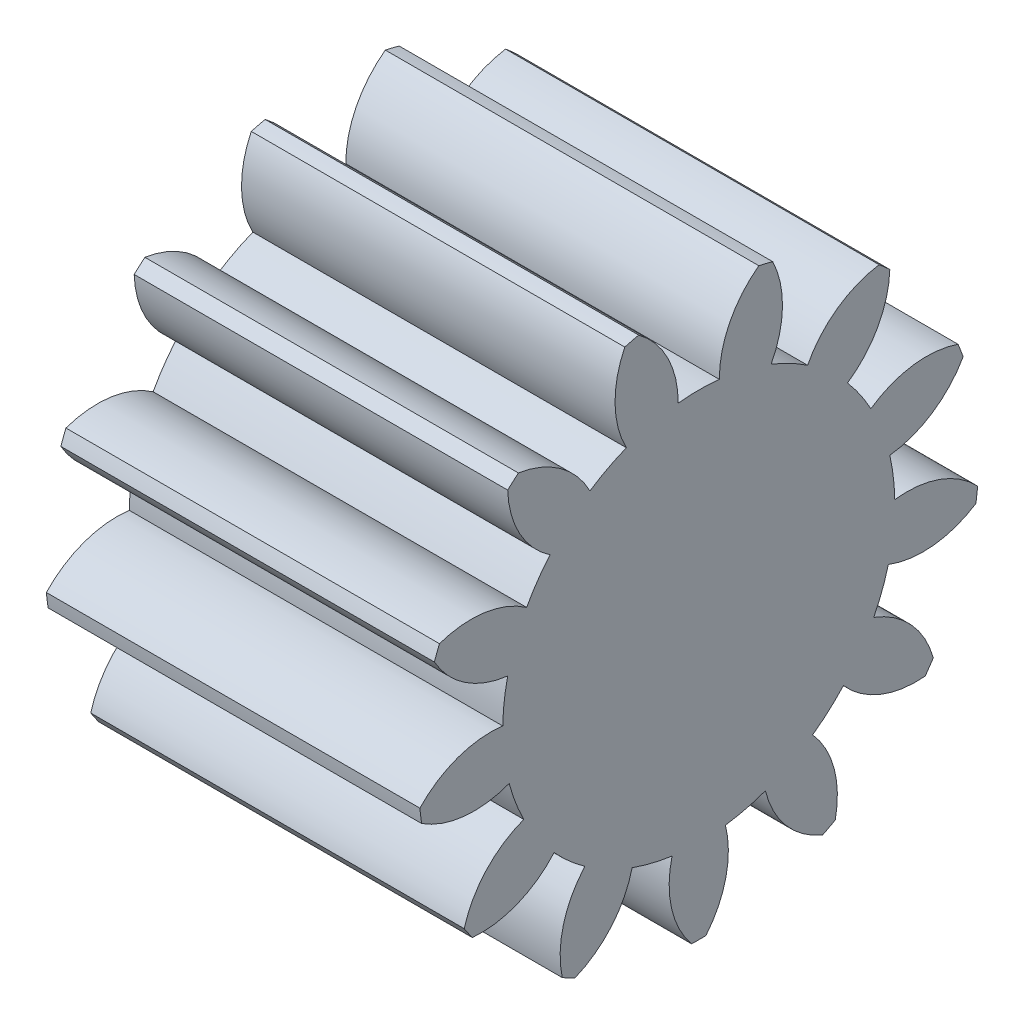
SolidWorks part; units mm, degrees
ref_plane "Plane1" through (0, 0, 0) normal (0, 0, 1) x (1, 0, 0)
ref_plane "Plane2" through (0, 0, 0) normal (0, 1, 0) x (1, 0, 0)
ref_plane "Plane3" through (0, 0, 0) normal (1, 0, 0) x (0, 0, -1)
sketch "HoldingSke" plane through (0, 0, 0) normal (0, 1, 0) x (1, 0, 0)
  line L0 (0, 0) -> (1.624, -0.3749)
  line L1 (-15, 0) -> (100, 0) construction
  line L2 (0, 0) -> (-2.1039, 2.3779)
  line L3 (0, 0) -> (-11.863, 4.5341)
  line L4 (0, 0) -> (8.4147, 1.9427)
  line L5 (0, 0) -> (-46.8476, -17.4728)
  line L6 (0, 0) -> (-1.8237, -1.2305)
  line L7 (-2.1039, 2.3779) -> (8.6586, 51.2059)
  line L8 (-76.2, 54.61) -> (-75.7, 54.61)
  line L9 (-71.009, 38.7566) -> (-53.1078, 45.2721)
  line L10 (-76.2, 71.12) -> (104.1128, 71.12)
  line L11 (0, 0) -> (-2.2, 0)
  line L12 (-76.2, 101.6) -> (-76.177, 101.6)
  line L13 (24.9733, 27.94) -> (52.9518, 28.4284)
  line L14 (24.9733, 27.94) -> (24.9743, 27.94)
  line L15 (24.9733, 27.94) -> (100.4006, 29.5858)
  line L16 (-63.627, -0.6) -> (-12.827, -0.6)
  circle A0 centre (0, 0) radius 1.5
  circle A1 centre (0, 0) radius 3.149
  circle A2 centre (0, 0) radius 37.5
  circle A3 centre (0, 0) radius 1.5
  dimension "MHD" = 6.298
  dimension "Hub_dia" = 75
  dimension "Bore" = 3
  dimension "MBD" = 3
  dimension "Num_teeth" = 13
  dimension "Pitch" = 1.6667
  dimension "Overall_len" = 50
  dimension "Show_teeth" = 13
  dimension "Thickness" = 2.2
  dimension "OAL" = 50.0001
  dimension "T_dim" = 0.5
  dimension "Ap" = 20
  dimension "H" = 19.05
  dimension "Pitch_radius" = 180.3128
  dimension "Width" = 2.2
  dimension "Backlash" = 0.023
  dimension "Addendum_fac" = 1
  dimension "Dedendum_fac" = 1.25
  dimension "Clearance_fac" = 0.25
  dimension "Dedendum_add" = 0.001
  dimension "Module" = 0.6
sketch "BasProSke" plane through (0, 0, 0) normal (0, 1, 0) x (1, 0, 0)
  line L0 (-10, 0) -> (60, 0) construction
  line L1 (0, 0) -> (0, 4.5)
  line L2 (0, 0) -> (6, 0)
  line L3 (6, 0) -> (6, 4.5)
  line L4 (6, 4.5) -> (0, 4.5)
  dimension "Thickness" = 6
  dimension "Diameter" = 9
revolve "Base-Revolve" add sketch "BasProSke" angle 360 about L0
sketch "TooCutSke" plane through (0, 0, 0) normal (1, 0, 0) x (0, 0, -1)
  line L1 (0, 0) -> (0, 107) construction
  line L2 (0, 0) -> (-0.5103, 3.8665) construction
  line L3 (0, 0) -> (-1.8553, 7.5272) construction
  line L4 (-0.5103, 3.8665) -> (-0.9276, 3.7636) construction
  arc A0 (0.3306, 3.1316) -> (-0.3306, 3.1316) centre (0, 0) ccw
  arc A1 (0.9926, 4.4152) -> (-0.9926, 4.4152) centre (0, 0) ccw
  circle A2 centre (0, 0) radius 3.9 construction
  circle A3 centre (0, 0) radius 3.6648 construction
  arc A4 (-0.3306, 3.1316) -> (-0.9926, 4.4152) centre (-1.8906, 3.1395) ccw
  arc A5 (0.9926, 4.4152) -> (0.3306, 3.1316) centre (1.8906, 3.1395) ccw
  dimension "Root_dia" = 6.298
  dimension "Overcut_dia" = 9.0508
  dimension "Pitch_dia" = 7.8
  dimension "Base_dia" = 7.3296
  dimension "Flank_rad" = 1.56
  dimension "Half_ang" = 13.846
  dimension "Half_CT" = 0.4298
extrude "ToothCut" cut sketch "TooCutSke" along normal through all
fillet "Breaks" [suppressed] radius 0.012 tangent propagation no
fillet "RootFillets" [suppressed] radius 0.151
pattern_circular "TeethCuts" count 13 over 360 about axis through (-10, 0, 0) along (1, 0, 0) of "ToothCut", "RootFillets", "Breaks"
sketch "HubNeaOneSke" plane through (0, 0, 0) normal (-1, 0, 0) x (0, 0, 1)
  circle A0 centre (0, 0) radius 3.149
  dimension "Diameter" = 6.298
extrude "HubNearOne" [suppressed] add sketch "HubNeaOneSke" along normal blind 44.0001
sketch "HubNeaBotSke" plane through (0, 0, 0) normal (-1, 0, 0) x (0, 0, 1)
  circle A0 centre (0, 0) radius 3.149
  dimension "Diameter" = 6.298
extrude "HubNearBoth" [suppressed] add sketch "HubNeaBotSke" along normal blind 22
ref_plane "FarPln" through (6, 0, 0) normal (1, 0, 0) x (0, 0, -1)
sketch "HubFarSke" plane through (6, 0, 0) normal (1, 0, 0) x (0, 0, -1)
  circle A0 centre (0, 0) radius 3.149
  dimension "Diameter" = 6.298
extrude "HubFar" [suppressed] add sketch "HubFarSke" along normal blind 22
sketch "BorSke" plane through (0, 0, 0) normal (1, 0, 0) x (0, 0, -1)
  line L0 (1.118, 1) -> (-1.118, 1) construction
  line L1 (1.118, -1) -> (-1.118, -1) construction
  line L2 (1.118, 1) -> (-1.118, 1)
  line L3 (1.118, -1) -> (-1.118, -1)
  circle A0 centre (0, 0) radius 1.5 construction
  arc A1 (-1.118, -1) -> (-1.118, 1) centre (0, 0) ccw
  arc A2 (1.118, 1) -> (1.118, -1) centre (0, 0) ccw
  dimension "Diameter" = 3
extrude "Bore" cut sketch "BorSke" along normal mid plane 100.0001 rebuild error yes
sketch "KeySke" plane through (0, 0, 0) normal (1, 0, 0) x (0, 0, -1)
  line L0 (-0.6, 0) -> (-0.6, 2)
  line L1 (-0.6, 2) -> (0.6, 2)
  line L2 (0.6, 2) -> (0.6, 0)
  line L3 (0, 0) -> (0, 34) construction
  line L4 (-0.6, 0) -> (0.6, 0)
  dimension "Offset" = 2
  dimension "Width" = 1.2
extrude "Keyway" [suppressed] cut sketch "KeySke" along normal mid plane 100.0001
pattern_circular "Keyway2" [suppressed] count 2 every 90 about axis through (-10, 0, 0) along (1, 0, 0) reverse direction yes
equation "' \"Module@HoldingSke\" = 6.35"
equation "' \"Num_teeth@HoldingSke\" = 12"
equation "' \"Ap@HoldingSke\" =  20"
equation "' \"Ap@HoldingSke\" = 20"
equation "' \"Width@HoldingSke\" = 0.5 * 25.4"
equation "' \"Hub_dia@HoldingSke\"= 1 * 25.4"
equation "' \"Hub_dia@HoldingSke\" = 1 * 25.4"
equation "' \"Overall_len@HoldingSke\" = 1.0 * 25.4"
equation "' \"Bore@HoldingSke\" = 0.75 * 25.4"
equation "' \"T_dim@HoldingSke\" = 0.1 * 25.4"
equation "' \"Width@KeySke\" = 0.25 * 25.4"
equation "' \"Show_teeth@HoldingSke\" = 13"
equation "' \"Backlash@HoldingSke\" = 0.009 * 25.4"
equation "' \"Addendum_fac@HoldingSke\" = 1.0"
equation "' \"Dedendum_fac@HoldingSke\" = 1.25"
equation "' \"Dedendum_add@HoldingSke\" = 0.00005 * 25.4"
equation "' \"Clearance_fac@HoldingSke\" = 0.25"
equation "\"Pitch@HoldingSke\" = 1 / \"Module@HoldingSke\""
equation "\"Overcut_dia@TooCutSke\" = (\"Num_teeth@HoldingSke\" + 2 * \"Addendum_fac@HoldingSke\") / \"Pitch@HoldingSke\" + 0.002 * 25.4"
equation "\"Pitch_dia@TooCutSke\" = \"Num_teeth@HoldingSke\" / \"Pitch@HoldingSke\""
equation "\"Base_dia@TooCutSke\" = \"Num_teeth@HoldingSke\" / \"Pitch@HoldingSke\" * cos((\"Ap@HoldingSke\"  * 3.14159265 / 180))"
equation "\"Root_dia@TooCutSke\" = (\"Num_teeth@HoldingSke\" + 2) / \"Pitch@HoldingSke\" - 2 * (\"Addendum_fac@HoldingSke\" + \"Dedendum_fac@HoldingSke\") / \"Pitch@HoldingSke\" - \"Dedendum_add@HoldingSke\" * 2"
equation "\"Half_ang@TooCutSke\" = 180 / \"Num_teeth@HoldingSke\""
equation "\"Half_CT@TooCutSke\" = \"Num_teeth@HoldingSke\" / \"Pitch@HoldingSke\" * sin((3.14159265 / 2 / \"Num_teeth@HoldingSke\")) / 2 - 7 * \"Backlash@HoldingSke\" / 4"
equation "\"Flank_rad@TooCutSke\" = \"Num_teeth@HoldingSke\" / \"Pitch@HoldingSke\" / 5"
equation "\"Radius@RootFillets\" = \"Clearance_fac@HoldingSke\" / \"Pitch@HoldingSke\" + \"Dedendum_add@HoldingSke\""
equation "\"Break_rad@Breaks\" = 0.02 / \"Pitch@HoldingSke\""
equation "\"Thickness@HoldingSke\" = \"Width@HoldingSke\""
equation "\"OAL@HoldingSke\" = \"Thickness@HoldingSke\""
equation "\"MHD@HoldingSke\" = (\"Num_teeth@HoldingSke\" + 2) / \"Pitch@HoldingSke\" - 2 * (\"Addendum_fac@HoldingSke\" + \"Dedendum_fac@HoldingSke\")  / \"Pitch@HoldingSke\" - \"Dedendum_add@HoldingSke\" * 2"
equation "\"MBD@HoldingSke\" = (\"Num_teeth@HoldingSke\" + 2) / \"Pitch@HoldingSke\" - 2 * (\"Addendum_fac@HoldingSke\" + \"Dedendum_fac@HoldingSke\")  / \"Pitch@HoldingSke\" - \"Dedendum_add@HoldingSke\" * 2 - 0.002 * 25.4"
equation "\"MHD@HoldingSke\" = ((sgn( \"MHD@HoldingSke\" - \"Hub_dia@HoldingSke\" )-1)*( \"MHD@HoldingSke\" - \"Hub_dia@HoldingSke\" ))/-2+ \"Hub_dia@HoldingSke\""
equation "\"MBD@HoldingSke\" = ((sgn( \"MBD@HoldingSke\" - \"Bore@HoldingSke\" )-1)*( \"MBD@HoldingSke\" - \"Bore@HoldingSke\" ))/-2+ \"Bore@HoldingSke\""
equation "\"OAL@HoldingSke\" = ((sgn( \"OAL@HoldingSke\" - \"Overall_len@HoldingSke\" )+1)*( \"OAL@HoldingSke\" - \"Overall_len@HoldingSke\" ))/2 + \"Overall_len@HoldingSke\" + 0.000002 * 25.4"
equation "\"Num_teeth@TeethCuts\" = int( \"Show_teeth@HoldingSke\" ) + 1"
equation "\"Num_teeth@TeethCuts\" = ((sgn( \"Num_teeth@TeethCuts\" - \"Num_teeth@HoldingSke\" )-1)*( \"Num_teeth@TeethCuts\" - \"Num_teeth@HoldingSke\" ))/-2+ \"Num_teeth@HoldingSke\""
equation "\"Num_teeth@TeethCuts\" = ((sgn( \"Num_teeth@TeethCuts\" - 2.0)+1)*( \"Num_teeth@TeethCuts\" - 2.0))/2 +2.0"
equation "\"Angle@TeethCuts\" = 360.0 / \"Num_teeth@HoldingSke\""
equation "\"Diameter@BasProSke\" = (\"Num_teeth@HoldingSke\" + 2 * \"Addendum_fac@HoldingSke\") / \"Pitch@HoldingSke\""
equation "' \"Fillet_rad@BasProSke\" =  \"Thickness@HoldingSke\" * 0.05"
equation "' \"Fillet_rad@BasProSke\" = \"Thickness@HoldingSke\" * 0.05"
equation "\"MHD@HoldingSke\" = ((sgn( \"MHD@HoldingSke\" - \"Root_dia@TooCutSke\" )-1)*( \"MHD@HoldingSke\" - \"Root_dia@TooCutSke\" ))/-2+ \"Root_dia@TooCutSke\""
equation "\"Diameter@HubNeaOneSke\" = \"MHD@HoldingSke\""
equation "\"Length@HubNearOne\" = \"OAL@HoldingSke\" - \"Thickness@BasProSke\""
equation "\"Diameter@HubNeaBotSke\" = \"MHD@HoldingSke\""
equation "\"Length@HubNearBoth\" = ( \"OAL@HoldingSke\" - \"Thickness@BasProSke\" ) / 2.0"
equation "\"Thickness@FarPln\" = \"Thickness@BasProSke\""
equation "\"Diameter@HubFarSke\" = \"MHD@HoldingSke\""
equation "\"Length@HubFar\" = ( \"OAL@HoldingSke\" - \"Thickness@BasProSke\" ) / 2.0"
equation "\"Diameter@BorSke\" = \"MBD@HoldingSke\""
equation "\"D1@Bore\" = \"OAL@HoldingSke\" * 2.0"
equation "\"D1@Keyway\" = \"OAL@HoldingSke\" * 2.0"
equation "\"Offset@KeySke\" = \"T_dim@HoldingSke\" + \"MBD@HoldingSke\" / 2.0"
